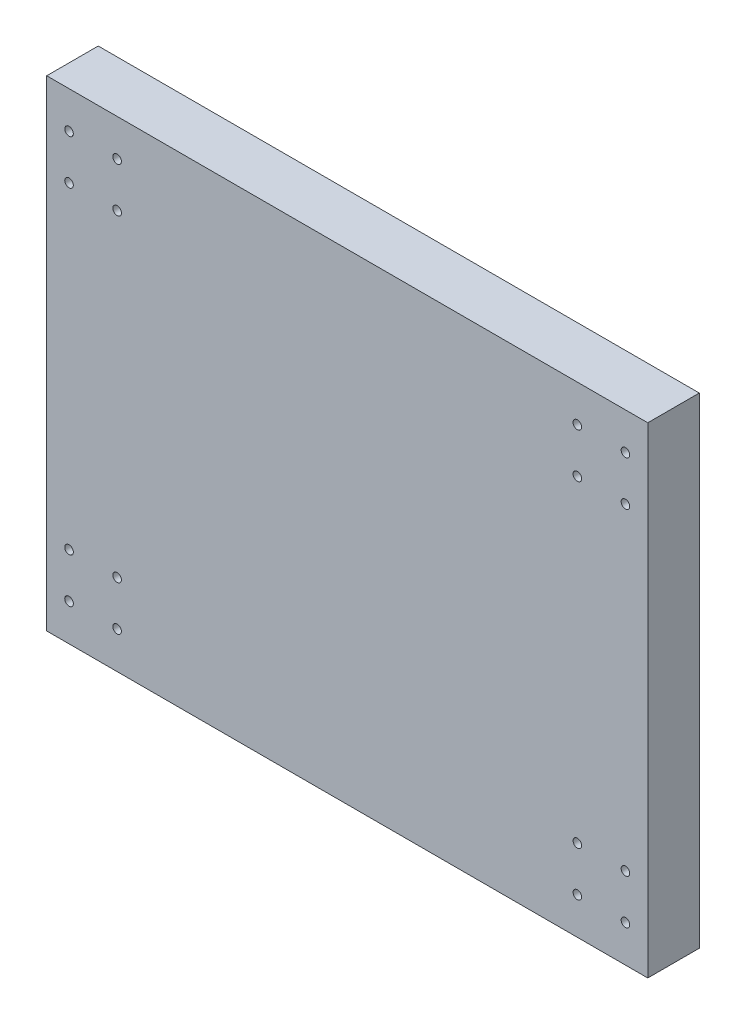
SolidWorks part; units mm, degrees
ref_plane "Plan de face" through (0, 0, 0) normal (0, 0, 1) x (1, 0, 0)
ref_plane "Plan de dessus" through (0, 0, 0) normal (0, 1, 0) x (1, 0, 0)
ref_plane "Plan de droite" through (0, 0, 0) normal (1, 0, 0) x (0, 0, -1)
sketch "Esquisse1" plane through (0, 0, 0) normal (0, 0, 1) x (1, 0, 0)
  line L1 (0, 0) -> (350, 0)
  line L2 (0, 0) -> (0, 280)
  line L3 (0, 280) -> (350, 280)
  line L4 (350, 0) -> (350, 280)
  dimension "D1" = 350
  dimension "D2" = 280
extrude "Boss.-Extru.1" add sketch "Esquisse1" along normal blind 30
sketch "Esquisse2" plane through (0, 0, 30) normal (0, 0, 1) x (1, 0, 0)
  line L0 (175, 280) -> (175, 0) construction
  line L1 (350, 280) -> (0, 280) construction
  line L2 (0, 0) -> (350, 0) construction
  line L3 (0, 140) -> (350, 140) construction
  line L4 (0, 280) -> (0, 0) construction
  line L5 (350, 0) -> (350, 280) construction
  line L6 (27, 280) -> (27, 140) construction
  line L7 (27, 245.5) -> (0, 245.5) construction
  line L8 (27, 34.5) -> (0, 34.5) construction
  line L9 (323, 34.5) -> (350, 34.5) construction
  line L10 (323, 245.5) -> (350, 245.5) construction
  line L11 (323, 280) -> (323, 140) construction
  circle A0 centre (13, 258.5) radius 2.5
  circle A1 centre (13, 232.5) radius 2.5
  circle A2 centre (41, 232.5) radius 2.5
  circle A3 centre (41, 258.5) radius 2.5
  circle A4 centre (41, 21.5) radius 2.5
  circle A5 centre (41, 47.5) radius 2.5
  circle A6 centre (13, 47.5) radius 2.5
  circle A7 centre (13, 21.5) radius 2.5
  circle A8 centre (337, 21.5) radius 2.5
  circle A9 centre (337, 47.5) radius 2.5
  circle A10 centre (309, 47.5) radius 2.5
  circle A11 centre (309, 21.5) radius 2.5
  circle A12 centre (309, 258.5) radius 2.5
  circle A13 centre (309, 232.5) radius 2.5
  circle A14 centre (337, 232.5) radius 2.5
  circle A15 centre (337, 258.5) radius 2.5
  dimension "D3" = 5
  dimension "D1" = 28
  dimension "D2" = 26
  dimension "D4" = 211
  dimension "D5" = 296
extrude "Enlèv. mat.-Extru.1" cut sketch "Esquisse2" against normal through all
